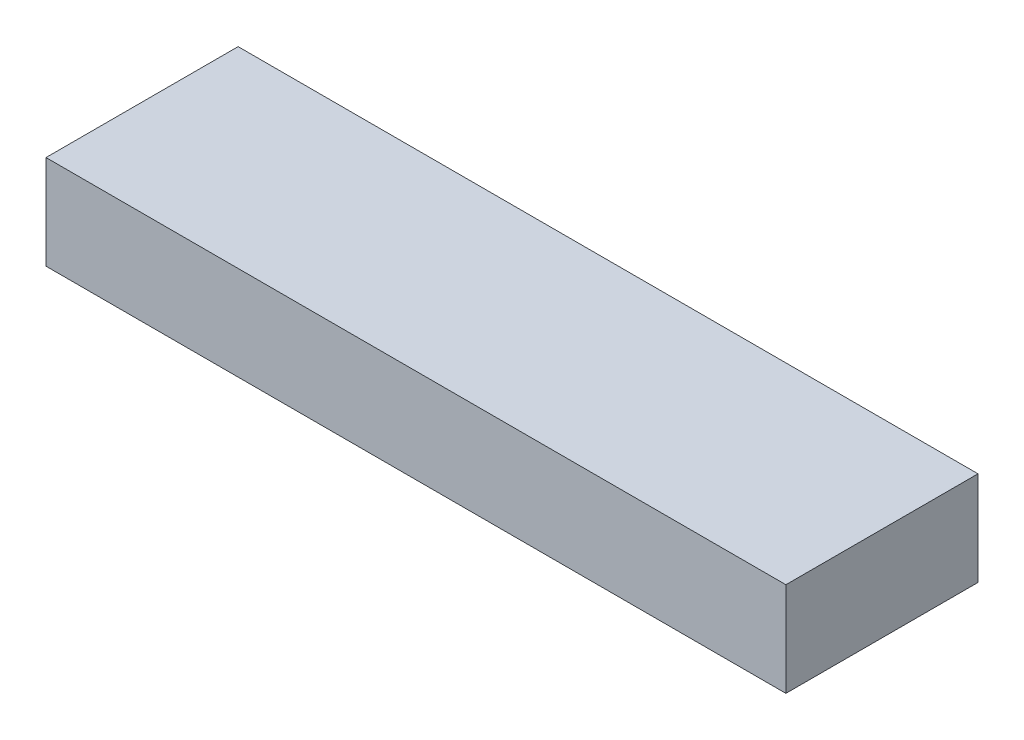
SolidWorks part; units mm, degrees
ref_plane "Front Plane" through (0, 0, 0) normal (0, 0, 1) x (1, 0, 0)
ref_plane "Top Plane" through (0, 0, 0) normal (0, 1, 0) x (1, 0, 0)
ref_plane "Right Plane" through (0, 0, 0) normal (1, 0, 0) x (0, 0, -1)
sketch "Sketch1" plane through (0, 0, 0) normal (0, 1, 0) x (1, 0, 0)
  line L1 (570, -148) -> (-570, -148)
  line L2 (570, -148) -> (570, 148)
  line L3 (570, 148) -> (-570, 148)
  line L4 (-570, -148) -> (-570, 148)
  line L5 (570, -148) -> (-570, 148) construction
  line L6 (570, 148) -> (-570, -148) construction
  point P0 (0, 0)
  dimension "D1" = 1140
  dimension "D2" = 296
extrude "Boss-Extrude1" add sketch "Sketch1" along normal blind 145
equation "\"thickness 1\" = 2"
equation "\"thickness 2\"= 3"
equation "\"connecting flange\"= 35"
equation "\"main length\"= 1200"
equation "\"main width\"= 1200"
equation "\"divider panel distance offset\"= 296"
equation "\"access hatch length\" = \"access hatch cutout length\" + \"access hatch offset\" * 2"
equation "\"access hatch width\" = \"access hatch cutout width\" + \"access hatch offset\" * 2"
equation "\"side panel length\"= 1200"
equation "\"side panel width\"= 950"
equation "\"drift eliminator size offset\"= 5"
equation "\"drift eliminator depth\" = \"divider panel distance offset\""
equation "\"D2@Sketch1\"=\"drift eliminator depth\""
equation "\"thickness radius 1\"= 3.7366"
equation "\"connecting flange holes\"= 8"
equation "\"connecting flange hole gap\"= 100"
equation "\"cut out flange\"= 15 "
equation "\"top panel slot length\"= 250"
equation "\"top panel slot width\"= 700"
equation "\"access hatch cutout length\"= 400"
equation "\"access hatch cutout width\"= 600"
equation "\"access hatch cutout offset X\"= 100"
equation "\"access hatch cutout offset Y\"= 100"
equation "\"slotted panel length\" = \"main length\" + 100"
equation "\"slotted panel width\" = \"main width\""
equation "\"slot count x\"= 4"
equation "\"slot count y\"= 9"
equation "\"slot offset\" = \"water tray depth\""
equation "\"slot length\"= 30"
equation "\"slot width\"= 200"
equation "\"slot offset x\" = \"slot length\" + \"slot offset\""
equation "\"slot offset y\" = \"slot width\" + \"slot offset\""
equation "\"guide rail flange\"= 40"
equation "\"guid rail flange mount side\"= 20"
equation "\"guid rail back length\" = \"main width\" - \"guide rail flange\" * 2"
equation "\"splash plate length\"= 400"
equation "\"splash plate width\" = \"main width\""
equation "\"splash plate air gap\"= 200"
equation "\"splash plate slot count\"= 11"
equation "\"splash plate slot length\"= 50"
equation "\"splash plate slot height\"= 50"
equation "\"splash plate slot offset\"= 65"
equation "\"water tray depth\"= 150"
equation "\"water tray width\"= 200"
equation "\"water tray panel length\"= 473"
equation "\"dimpled panel length\" = \"main length\" - 200 - \"water tray depth\"/2"
equation "\"dimpled panel top offset\" = \"water tray depth\"/2"
equation "\"dimpled panel width\" = \"main width\""
equation "\"dimple panel slot count\"= 36"
equation "\"dimple panel slot length\"= 8"
equation "\"dimple panel slot width\"= 8"
equation "\"dimple panel slot offset\"= 25"
equation "\"sump base flat section width\"= 300"
equation "\"sump upper depth\"= 300"
equation "\"sump depth\"= 550"
equation "\"leg length\" = \"sump depth\" + 150"
equation "\"leg width\"= 80"
equation "\"leg depth\"= 40"
equation "\"leg support plate size\" = \"leg width\" - \"thickness 2\" * 2"
equation "\"leg base plate thickness\"= 8"
